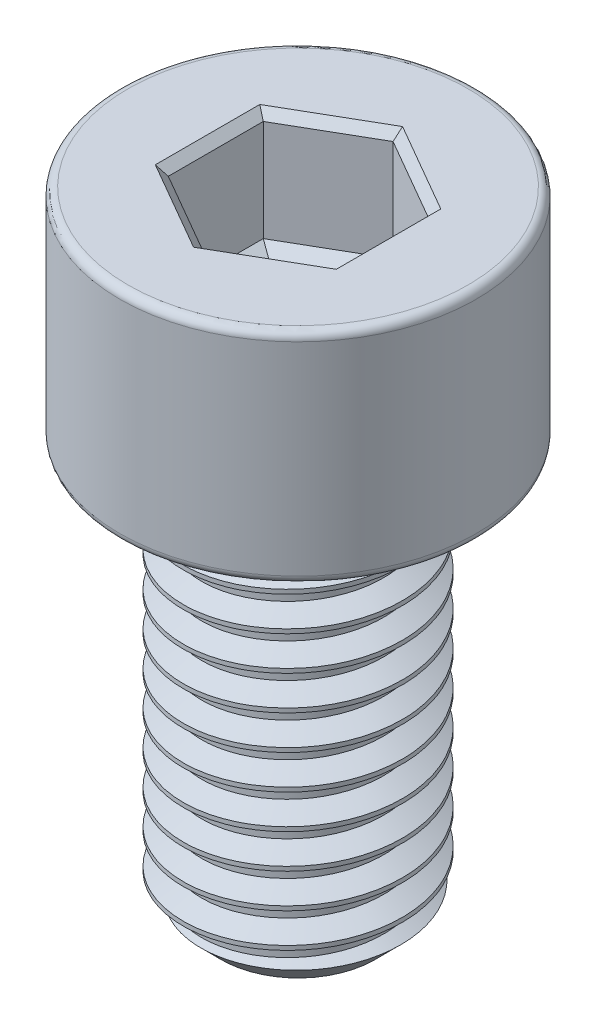
SolidWorks part; units mm, degrees
material "AISI Type A2 Tool Steel"
ref_plane "Front Plane" through (0, 0, 0) normal (0, 0, 1) x (1, 0, 0)
ref_plane "Top Plane" through (0, 0, 0) normal (0, 1, 0) x (1, 0, 0)
ref_plane "Right Plane" through (0, 0, 0) normal (1, 0, 0) x (0, 0, -1)
sketch "Sketch1" plane through (0, 0, 0) normal (0, 1, 0) x (1, 0, 0)
  circle A0 centre (0, 0) radius 4
  dimension "D1" = 8
extrude "Boss-Extrude1" add sketch "Sketch1" along normal blind 15
thread "Thread1" pitch 1.25 method cut profile "Thread Profile1" start angle 0, offset 1.25, length 0, pitch 1.25, diameter 8
ref_plane "Plane1" through (-4, 16.25, 0) normal (0, 0, 1) x (-1, 0, 0)
sketch "Thread Profile1" plane through (-4, 16.25, 0) normal (0, 0, 1) x (-1, 0, 0)
  line L0 (0, 0) -> (0, 1.25) construction
  line L11 (0, 0) -> (0, 1.0937)
  line L12 (0, 1.0937) -> (-0.6766, 0.7031)
  line L13 (-0.6766, 0.7031) -> (-0.6766, 0.3906)
  line L15 (-0.6766, 0.3906) -> (0, 0)
  line L17 (-0.6766, 0.5469) -> (0, 0.5469) construction
  point P2 (0, 0)
  dimension "Pitch" = 1.25
  dimension "Profile_Angle" = 60
  dimension "Profile_Land" = 0.3125
  dimension "Profile_Height" = 0.6766
sketch "Sketch2" plane through (0, 15, 0) normal (0, 1, 0) x (1, 0, 0)
  circle A0 centre (0, 0) radius 6.5
  dimension "D1" = 13
extrude "Boss-Extrude2" add sketch "Sketch2" along normal blind 8
sketch "Sketch5" plane through (0, 0, 0) normal (0, 0, 1) x (1, 0, 0)
  line L0 (0, 0) -> (0, 0.9986) construction
  line L1 (0, 0) -> (4.01, 0) construction
  line L2 (4.01, 0) -> (4.01, 1.2)
  line L3 (4.01, 1.2) -> (2.81, 0)
  line L4 (2.81, 0) -> (4.01, 0)
  dimension "D1" = 1.2
  dimension "D2" = 45
  dimension "D3" = 4.01
revolve "Cut-Revolve1" cut sketch "Sketch5" angle 360 about L0
fillet "Fillet1" radius 0.3 2 edges at (0, 23, 6.5) (0, 15, 6.5)
sketch "Sketch6" plane through (0, 23, 0) normal (0, 1, 0) x (1, 0, 0)
  line L1 (0, 3.4641) -> (-3, 1.7321)
  line L2 (-3, 1.7321) -> (-3, -1.7321)
  line L3 (-3, -1.7321) -> (0, -3.4641)
  line L4 (0, -3.4641) -> (3, -1.7321)
  line L5 (3, -1.7321) -> (3, 1.7321)
  line L6 (3, 1.7321) -> (0, 3.4641)
  circle A0 centre (0, 0) radius 3 construction
  dimension "D1" = 6
extrude "Cut-Extrude1" cut sketch "Sketch6" against normal blind 4
chamfer "Chamfer1" distance 0.3 angle 45 6 edges at (-3, 23, 0) (-1.5, 23, 2.5981) (1.5, 23, 2.5981) (3, 23, 0) (1.5, 23, -2.5981) (-1.5, 23, -2.5981)
sketch "Sketch7" plane through (0, 19, 0) normal (0, 1, 0) x (1, 0, 0)
  line L1 (0, 3.4641) -> (-3, 1.7321)
  line L2 (-3, 1.7321) -> (-3, -1.7321)
  line L3 (-3, -1.7321) -> (0, -3.4641)
  line L4 (0, -3.4641) -> (3, -1.7321)
  line L5 (3, -1.7321) -> (3, 1.7321)
  line L6 (3, 1.7321) -> (0, 3.4641)
  circle A0 centre (0, 0) radius 3 construction
extrude "Cut-Extrude2" cut sketch "Sketch7" against normal blind 0.4 draft 60
